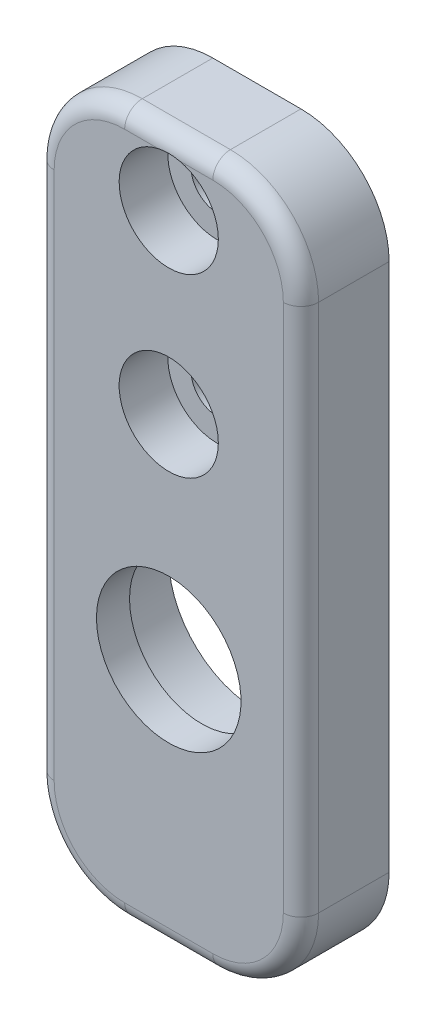
SolidWorks part; units mm, degrees
material "6061 Alloy"
ref_plane "Front Plane" through (0, 0, 0) normal (0, 0, 1) x (1, 0, 0)
ref_plane "Top Plane" through (0, 0, 0) normal (0, 1, 0) x (1, 0, 0)
ref_plane "Right Plane" through (0, 0, 0) normal (1, 0, 0) x (0, 0, -1)
sketch "Sketch1" plane through (0, 0, 0) normal (1, 0, 0) x (0, 0, -1)
  line L0 (0, 0) -> (0, 50.8)
  line L1 (0, 50.8) -> (6.35, 50.8)
  line L2 (6.35, 50.8) -> (6.35, 0)
  line L3 (0, 0) -> (6.35, 0)
extrude "Body" add sketch "Sketch1" along normal blind 19.05
sketch "Sketch2" plane through (0, 0, -6.35) normal (0, 0, -1) x (-1, 0, 0)
  line L0 (-9.525, 0) -> (-9.525, 18.034) construction
  line L1 (-19.05, 0) -> (0, 0) construction
  circle A0 centre (-9.525, 18.034) radius 6.35
  circle A1 centre (-9.525, 18.034) radius 5.207
  dimension "D1" = 12.7
  dimension "D3" = 10.414
  dimension "D2" = 18.034
extrude "Pitch Axle Opening" cut sketch "Sketch2" against normal blind 6.35 contours A1 region at (9.525, 18.034, -6.35)
hole_wizard "CBORE for #6 Socket Head Cap Screw1" positions "Sketch4" profile "Sketch3" counterbore size "#6" standard "Ansi Inch" end condition through all
sketch "Sketch4" plane through (0, 0, 0) normal (0, 0, 1) x (1, 0, 0)
  line L0 (0, 50.8) -> (19.05, 50.8)
  line L1 (9.525, 50.8) -> (9.525, 0) construction
  line L5 (0, 46.0375) -> (19.05, 46.0375) construction
  line L6 (0, 33.3375) -> (19.05, 33.3375) construction
  line L7 (19.05, 0) -> (0, 0) construction
  line L8 (19.05, 50.8) -> (19.05, 0) construction
  line L9 (0, 50.8) -> (0, 0) construction
  point P0 (9.525, 46.0375)
  point P1 (9.525, 33.3375)
  dimension "D1" = 4.7625
  dimension "D2" = 12.7
sketch "Sketch3" plane through (9.525, 46.0375, 0) normal (1, 0, 0) x (0, -1, 0)
  line L0 (0, 0) -> (0, 6.35)
  line L1 (0, 6.35) -> (1.8986, 6.35)
  line L3 (1.8986, 6.35) -> (1.8986, 3.5052)
  line L4 (1.8986, 3.5052) -> (3.5725, 3.5052)
  line L5 (3.5725, 3.5052) -> (3.5725, 0)
  line L7 (3.5725, 0) -> (0, 0)
  line L11 (0, -6.35) -> (0, 107.95) construction
  dimension "Thru Hole Dia." = 3.7973
  dimension "Thru Hole Depth" = 6.35
  dimension "C'Bore Dia." = 7.145
  dimension "C'Bore Depth" = 3.5052
fillet "Fillet1" radius 6.35 4 edges at (0, 50.8, -3.175) (19.05, 50.8, -3.175) (0, 0, -3.175) (19.05, 0, -3.175)
fillet "Fillet2" radius 1.27 8 edges at (17.1901, 48.9401, 0) (9.525, 50.8, 0) (1.8599, 48.9401, 0) (0, 25.4, 0) (1.8599, 1.8599, 0) (9.525, 0, 0) (17.1901, 1.8599, 0) (19.05, 25.4, 0)
extrude "Bearing Recess" cut sketch "Sketch2<3>" against normal blind 3.9675
sketch "Sketch2<3>" plane through (0, 0, -6.35) normal (0, 0, -1) x (-1, 0, 0) same geometry as "Sketch2"
